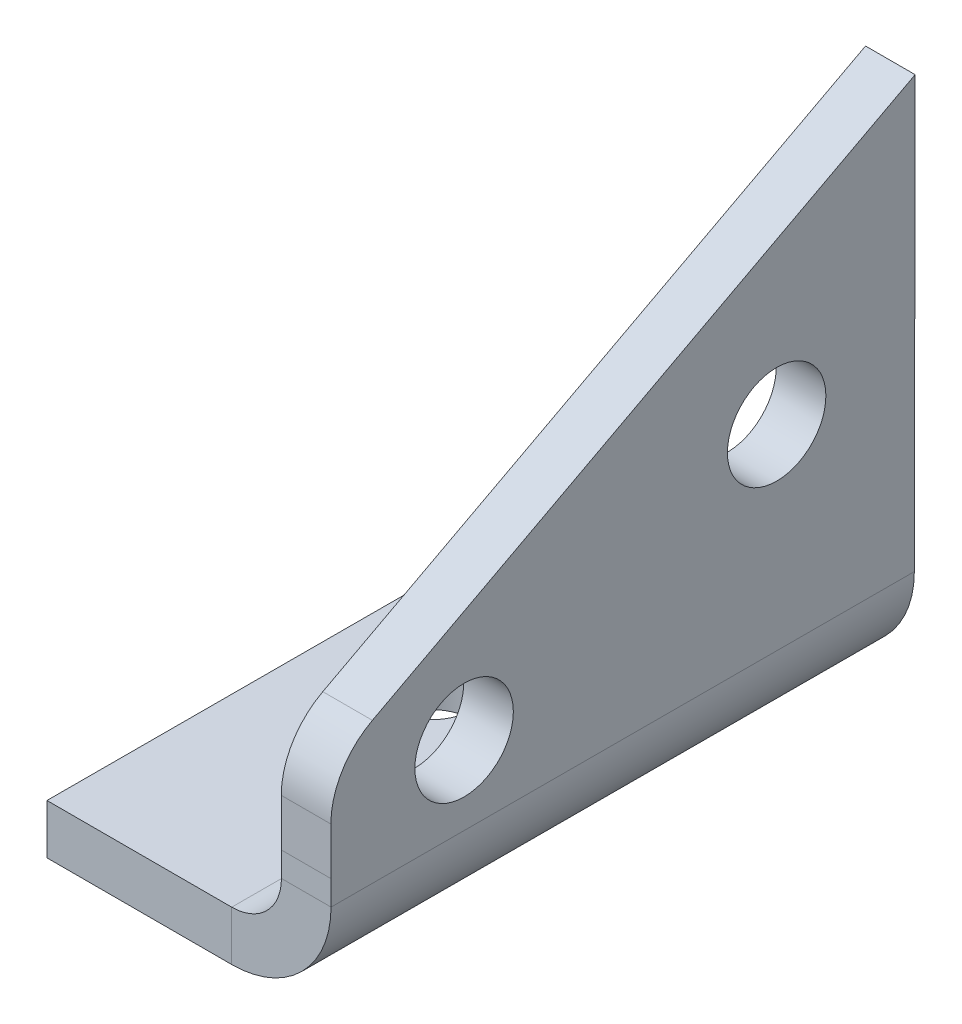
SolidWorks part; units mm, degrees
note: The reader was unsure of these and kept them because the rebuilt part matched: flange length of "Edge-Flange1".
ref_plane "Front Plane" through (0, 0, 0) normal (0, 0, 1) x (1, 0, 0)
ref_plane "Top Plane" through (0, 0, 0) normal (0, 1, 0) x (1, 0, 0)
ref_plane "Right Plane" through (0, 0, 0) normal (1, 0, 0) x (0, 0, -1)
sketch "Sketch2" plane through (0, 0, 0) normal (1, 0, 0) x (0, 0, -1)
  line L0 (83.1061, 32.1051) -> (83.1692, 65.9702)
  line L1 (83.1692, 65.9702) -> (48.4379, 47.5536)
  line L2 (45.7802, 43.1362) -> (45.7802, 32.1746)
  line B0 (99.7947, 74.138) -> (132.5557, 74.2809)
  line B1 (137.5775, 69.3044) -> (137.7293, 36.9329)
  line B2 (84.2276, -6.2892) -> (84.2276, 32.103)
  line B3 (84.2276, 32.103) -> (45.7802, 32.1746)
  line B4 (48.4379, 47.5536) -> (97.4741, 73.5555)
  line B5 (84.2276, -6.2892) -> (105.2373, -6.2892)
  arc B6 (137.5775, 69.3044) -> (132.5557, 74.2809) centre (132.5775, 69.2809) ccw
  arc B7 (45.7802, 43.1362) -> (48.4379, 47.5536) centre (50.7802, 43.1362) cw
  circle B8 centre (101.1736, 39.1798) radius 1.5
  ellipse B9 centre (132.1723, 39.3181) end of major axis (131.4323, 40.6229) minor radius 1.5
  spline B10 degree 3 poles (111.6938, 43.5404) (116.3311, 42.6396) (120.9601, 43.582) (124.8762, 46.224) (127.4831, 50.1636) (128.3839, 54.8009) (127.4416, 59.43) (124.7995, 63.346) (120.8599, 65.9529) (116.2226, 66.8538) (111.5936, 65.9114) (107.6775, 63.2693) (105.0706, 59.3298) (104.1698, 54.6924) (105.1121, 50.0634) (107.7542, 46.1473) (111.6938, 43.5404) (116.3311, 42.6396) (120.9601, 43.582) knots -1.178097 -0.785398 -0.392699 0 0.392699 0.785398 1.178097 1.570796 1.963495 2.356194 2.748894 3.141593 3.534292 3.926991 4.31969 4.712389 5.105088 5.497787 5.890486 6.283185 6.675884 7.068583 7.461283 only from (116.3297, 42.9468) to (116.3297, 42.9468)
sketch_block_instance "motormount-1"
sketch_block "Block1" parameters "D1"=5
sketch "Sketch3" plane through (0, 0, 0) normal (1, 0, 0) x (0, 0, -1)
  line L0 (84.2276, 32.103) -> (45.7802, 32.1746) construction
  line L1 (45.7802, 43.1362) -> (45.7802, 32.1746) construction
  line L2 (83.1692, 65.9702) -> (48.4379, 47.5536) construction
  line L3 (83.1061, 32.1051) -> (83.1692, 65.9702) construction
  line L4 (83.1061, 32.1051) -> (45.7802, 32.1746)
  line L5 (45.7802, 43.1362) -> (45.7802, 32.1746)
  line L6 (83.1692, 65.9702) -> (48.4379, 47.5536)
  line L7 (83.1061, 32.1051) -> (83.1692, 65.9702)
  arc A0 (48.4379, 47.5536) -> (45.7802, 43.1362) centre (50.7802, 43.1362) ccw construction
  arc A1 (48.4379, 47.5536) -> (45.7802, 43.1362) centre (50.7802, 43.1362) ccw
base flange "Base-Flange1" sketch "Sketch3" thickness 3.175 reverse thickness direction no parameters "D1"=3.175
edge flange "Edge-Flange1" sketch "Sketch13" flange angle 90 flange length 15 flange position material inside bend radius 3.175 thickness 3.175 relief rectangular parameters "D6"=10
sketch "Sketch13" plane through (-3.175, 32.2598, -0.0601) normal (0, -1, 0.0019) x (0, 0.0019, 1)
  line L0 (-45.7202, 0) -> (-83.0462, 0) construction
  line L1 (-45.7202, 0) -> (-83.0462, 0)
  line L2 (-83.0462, 0) -> (-83.0462, 15)
  line L3 (-83.0462, 15) -> (-45.7202, 15)
  line L4 (-45.7202, 15) -> (-45.7202, 0)
bend "EdgeBend1" bend radius 3.175 bend angle 90 parameters "D5"=1
sketch "Sketch15" plane through (0, 35.4348, -0.066) normal (0, 1, -0.0019) x (1, 0, 0)
  line L0 (-12.2625, 83.0462) -> (-12.2625, 45.7334) construction
  line L1 (-18.175, 83.0462) -> (-6.35, 83.0462) construction
  line L2 (-19.341, 123.6071) -> (-19.3381, 109.6071)
  line L3 (-8.3381, 109.6093) -> (-8.341, 123.6093)
  line L4 (-19.3418, 127.5571) -> (-19.3373, 105.6571)
  line L5 (-10.123, 105.659) -> (-10.1275, 127.559)
  line L6 (-8.8373, 105.6592) -> (-8.8418, 127.5592)
  line L7 (-1.8383, 110.6107) -> (-1.8408, 122.6107)
  line L8 (-0.0111, 99.672) -> (-0.0106, 97.3526)
  line L9 (3.1644, 97.3532) -> (3.1639, 99.6727)
  line L10 (3.1641, 98.5178) -> (3.1567, 134.5174)
  line L11 (-0.0178, 132.4327) -> (-0.0111, 99.672)
  line L12 (-0.0178, 132.4327) -> (3.1572, 132.4334)
  line L13 (-0.0189, 137.4637) -> (-0.0178, 132.4327)
  line L14 (-0.0189, 137.4637) -> (3.1561, 137.4644)
  line L15 (13.1561, 137.5329) -> (3.1561, 137.5309)
  line L16 (43.1561, 137.5391) -> (43.1567, 134.5257)
  line L17 (43.1561, 137.5391) -> (33.1561, 137.537)
  line L18 (13.1561, 137.5463) -> (33.1561, 137.5505)
  line L19 (43.1567, 134.5257) -> (43.1641, 98.526)
  line L20 (43.1648, 95.5395) -> (33.1648, 95.5374)
  line L21 (13.1648, 95.5468) -> (33.1648, 95.5509)
  line L22 (13.1648, 95.5333) -> (3.1648, 95.5313)
  line L23 (-0.0111, 99.672) -> (3.1639, 99.6727)
  line L24 (-0.0106, 97.3526) -> (3.1644, 97.3532)
  line L25 (-377.5488, 45.6583) -> (22.4512, 45.7405)
  line L26 (-0.0005, 48.3648) -> (0, 45.7154)
  line L27 (3.175, 45.7161) -> (3.1745, 48.3655)
  line L28 (3.1644, 97.3532) -> (3.1745, 48.3655)
  line L29 (-0.0106, 97.3526) -> (-0.0005, 48.3648)
  line L30 (-0.0005, 48.3648) -> (3.1745, 48.3655)
  line L31 (-377.5564, 82.6583) -> (22.4436, 82.7405)
  circle A1 centre (-12.2625, 64.3898) radius 2.65
  point P48 (0, 0)
  point P49 (-12.2625, 64.3898)
  dimension "D2" = 5.3
extrude "Cut-Extrude2" cut sketch "Sketch15" against normal blind 10
sketch "Sketch19" plane through (-3.175, 0, 0) normal (-1, 0, 0) x (0, 0, 1)
  line L0 (-45.7802, 43.5246) -> (-83.1267, 43.5246) construction
  line L3 (-43.6242, 51.0246) -> (-89.8692, 51.0246) construction
  line L4 (-54.2242, 35.3339) -> (-54.3064, 35.3337)
  line L5 (-54.3064, 35.3337) -> (-54.3064, 53.5849) construction
  line L7 (-74.2242, 35.2966) -> (-74.3064, 35.2965)
  line L8 (-74.3064, 35.2965) -> (-74.3064, 62.4144) construction
  circle A0 centre (-54.3064, 43.5246) radius 3.15
  circle A1 centre (-74.3064, 51.0246) radius 3.15
  point P2 (0, 0)
  point P17 (0, 0)
  dimension "D2" = 6.3
  dimension "D3" = 6.3
  dimension "D1" = 5
  dimension "D4" = 12.5
extrude "Cut-Extrude4" cut sketch "Sketch19" against normal blind 10 contours A1 | A0 normal cut yes
sketch "Bend-Lines1" [suppressed] plane through (0, 0, 0) normal (0, 1, 0) x (1, 0, 0)
sketch "Bounding-Box1" [suppressed] plane through (0, 0, 0) normal (0, 1, 0) x (1, 0, 0)
sheet metal parameters "Sheet-Metal1" thickness 3.175 parameters "D1"=3.175
flat pattern "Flat-Pattern1" [suppressed]
sketch "Bend-Lines2" plane through (0, 0, 0) normal (0, 1, 0) x (1, 0, 0)
sketch3d "Bounding-Box2" [suppressed]
  line L0 (4.9369, 22.9035, 0) -> (-32.389, 22.834, 0) construction
  line L1 (5, -10.9616, 0) -> (-32.3259, -11.0311, 0) construction
  line L2 (4.9369, 22.9035, 0) -> (5, -10.9616, 0) construction
  line L3 (-32.389, 22.834, 0) -> (-32.3259, -11.0311, 0) construction
sheet metal parameters "Sheet-Metal3" thickness 3.175 parameters "D1"=3.175
flat pattern "Flat-Pattern1" [suppressed]
sketch "Bend-Lines2" plane through (0, 0, 0) normal (1, 0, 0) x (0, 0, -1)
  line L0 (45.7854, 34.9338) -> (83.1113, 34.8642) construction
  line L1 (45.7854, 34.9338) -> (83.1113, 34.8642) construction
sketch3d "Bounding-Box2" [suppressed]
  line L0 (32.3024, -23.6878, 0) -> (32.389, 22.834, 0) construction
  line L1 (-5.0236, -23.6182, 0) -> (-4.9369, 22.9035, 0) construction
  line L2 (32.3024, -23.6878, 0) -> (-5.0236, -23.6182, 0) construction
  line L3 (32.389, 22.834, 0) -> (-4.9369, 22.9035, 0) construction
bend of the flat pattern "Flatten-<EdgeBend1>1"
sketch "Sketch14-1" [suppressed] plane through (-3.175, 37.7781, -0.0704) normal (-1, 0, 0) x (0, 1, -0.0019)
  line L5 (-12.2625, 83.0462) -> (-12.2625, 45.7202) construction
  line L6 (-18.175, 83.0462) -> (28.3468, 83.0462) construction
  circle A0 centre (-12.2625, 73.0462) radius 3.15
  circle A1 centre (-12.2625, 53.0462) radius 3.15
  dimension "D1" = 6.3
  dimension "D2" = 6.3
  dimension "D3" = 10
  dimension "D4" = 20
sketch "Sketch15-2" [suppressed] plane through (-3.175, 37.7781, -0.0704) normal (-1, 0, 0) x (0, 1, -0.0019)
sheet metal parameters "Sheet-Metal5" thickness 3.175 parameters "D1"=3.175
flat pattern "Flat-Pattern1" [suppressed]
sketch "Bend-Lines2" plane through (0, 0, 0) normal (1, 0, 0) x (0, 0, -1)
  line L0 (45.7854, 34.9338) -> (83.1113, 34.8642) construction
  line L1 (45.7854, 34.9338) -> (83.1113, 34.8642) construction
sketch3d "Bounding-Box2" [suppressed]
  line L0 (32.3024, -23.6878, 0) -> (32.389, 22.834, 0) construction
  line L1 (-5.0236, -23.6182, 0) -> (-4.9369, 22.9035, 0) construction
  line L2 (32.3024, -23.6878, 0) -> (-5.0236, -23.6182, 0) construction
  line L3 (32.389, 22.834, 0) -> (-4.9369, 22.9035, 0) construction
bend of the flat pattern "Flatten-<EdgeBend1>1"
sketch "Sketch15-2" [suppressed] plane through (-3.175, 37.7781, -0.0704) normal (-1, 0, 0) x (0, 1, -0.0019)
  line L0 (-12.2625, 83.0462) -> (-12.2625, 45.7334) construction
  line L2 (-19.341, 123.6071) -> (-19.3381, 109.6071)
  line L3 (-8.3381, 109.6093) -> (-8.341, 123.6093)
  line L4 (-19.3418, 127.5571) -> (-19.3373, 105.6571)
  line L5 (-10.123, 105.659) -> (-10.1275, 127.559)
  line L6 (-8.8373, 105.6592) -> (-8.8418, 127.5592)
  line L7 (-1.8383, 110.6107) -> (-1.8408, 122.6107)
  line L8 (-0.0111, 99.672) -> (-0.0106, 97.3526)
  line L9 (3.1644, 97.3532) -> (3.1639, 99.6727)
  line L10 (3.1641, 98.5178) -> (3.1567, 134.5174)
  line L11 (-0.0178, 132.4327) -> (-0.0111, 99.672)
  line L12 (-0.0178, 132.4327) -> (3.1572, 132.4334)
  line L13 (-0.0189, 137.4637) -> (-0.0178, 132.4327)
  line L14 (-0.0189, 137.4637) -> (3.1561, 137.4644)
  line L15 (13.1561, 137.5329) -> (3.1561, 137.5309)
  line L16 (43.1561, 137.5391) -> (43.1567, 134.5257)
  line L17 (43.1561, 137.5391) -> (33.1561, 137.537)
  line L18 (13.1561, 137.5463) -> (33.1561, 137.5505)
  line L19 (43.1567, 134.5257) -> (43.1641, 98.526)
  line L20 (43.1648, 95.5395) -> (33.1648, 95.5374)
  line L21 (13.1648, 95.5468) -> (33.1648, 95.5509)
  line L22 (13.1648, 95.5333) -> (3.1648, 95.5313)
  line L23 (-0.0111, 99.672) -> (3.1639, 99.6727)
  line L24 (-0.0106, 97.3526) -> (3.1644, 97.3532)
  line L25 (-377.5488, 45.6583) -> (22.4512, 45.7405)
  line L26 (-0.0005, 48.3648) -> (0, 45.7154)
  line L27 (3.175, 45.7161) -> (3.1745, 48.3655)
  line L28 (3.1644, 97.3532) -> (3.1745, 48.3655)
  line L29 (-0.0106, 97.3526) -> (-0.0005, 48.3648)
  line L30 (-0.0005, 48.3648) -> (3.1745, 48.3655)
  line L31 (-377.5564, 82.6583) -> (22.4436, 82.7405)
  line L32 (-377.5547, 74.1583) -> (22.4453, 74.2405)
  line L33 (-377.5505, 54.1583) -> (22.4495, 54.2405)
  circle A0 centre (-12.2625, 74.2334) radius 3.15
  circle A1 centre (-12.2625, 54.2334) radius 3.15
  dimension "D1" = 6.3
sheet metal parameters "Sheet-Metal7" thickness 3.175 parameters "D1"=3.175
flat pattern "Flat-Pattern1" [suppressed]
sketch "Bend-Lines2" plane through (0, 0, 0) normal (1, 0, 0) x (0, 0, -1)
  line L0 (45.7854, 34.9338) -> (83.1113, 34.8642) construction
  line L1 (45.7854, 34.9338) -> (83.1113, 34.8642) construction
sketch3d "Bounding-Box2" [suppressed]
  line L0 (32.3024, -23.6878, 0) -> (32.389, 22.834, 0) construction
  line L1 (-5.0236, -23.6182, 0) -> (-4.9369, 22.9035, 0) construction
  line L2 (32.3024, -23.6878, 0) -> (-5.0236, -23.6182, 0) construction
  line L3 (32.389, 22.834, 0) -> (-4.9369, 22.9035, 0) construction
bend of the flat pattern "Flatten-<EdgeBend1>1"
sketch "Sketch15-2" [suppressed] plane through (-3.175, 37.7781, -0.0704) normal (-1, 0, 0) x (0, 1, -0.0019)
  line L0 (-12.2625, 83.0462) -> (-12.2625, 45.7334) construction
  line L2 (-19.341, 123.6071) -> (-19.3381, 109.6071)
  line L3 (-8.3381, 109.6093) -> (-8.341, 123.6093)
  line L4 (-19.3418, 127.5571) -> (-19.3373, 105.6571)
  line L5 (-10.123, 105.659) -> (-10.1275, 127.559)
  line L6 (-8.8373, 105.6592) -> (-8.8418, 127.5592)
  line L7 (-1.8383, 110.6107) -> (-1.8408, 122.6107)
  line L8 (-0.0111, 99.672) -> (-0.0106, 97.3526)
  line L9 (3.1644, 97.3532) -> (3.1639, 99.6727)
  line L10 (3.1641, 98.5178) -> (3.1567, 134.5174)
  line L11 (-0.0178, 132.4327) -> (-0.0111, 99.672)
  line L12 (-0.0178, 132.4327) -> (3.1572, 132.4334)
  line L13 (-0.0189, 137.4637) -> (-0.0178, 132.4327)
  line L14 (-0.0189, 137.4637) -> (3.1561, 137.4644)
  line L15 (13.1561, 137.5329) -> (3.1561, 137.5309)
  line L16 (43.1561, 137.5391) -> (43.1567, 134.5257)
  line L17 (43.1561, 137.5391) -> (33.1561, 137.537)
  line L18 (13.1561, 137.5463) -> (33.1561, 137.5505)
  line L19 (43.1567, 134.5257) -> (43.1641, 98.526)
  line L20 (43.1648, 95.5395) -> (33.1648, 95.5374)
  line L21 (13.1648, 95.5468) -> (33.1648, 95.5509)
  line L22 (13.1648, 95.5333) -> (3.1648, 95.5313)
  line L23 (-0.0111, 99.672) -> (3.1639, 99.6727)
  line L24 (-0.0106, 97.3526) -> (3.1644, 97.3532)
  line L25 (-377.5488, 45.6583) -> (22.4512, 45.7405)
  line L26 (-0.0005, 48.3648) -> (0, 45.7154)
  line L27 (3.175, 45.7161) -> (3.1745, 48.3655)
  line L28 (3.1644, 97.3532) -> (3.1745, 48.3655)
  line L29 (-0.0106, 97.3526) -> (-0.0005, 48.3648)
  line L30 (-0.0005, 48.3648) -> (3.1745, 48.3655)
  line L31 (-377.5564, 82.6583) -> (22.4436, 82.7405)
  circle A1 centre (-12.2625, 64.3898) radius 2.65
  dimension "D2" = 5.3
